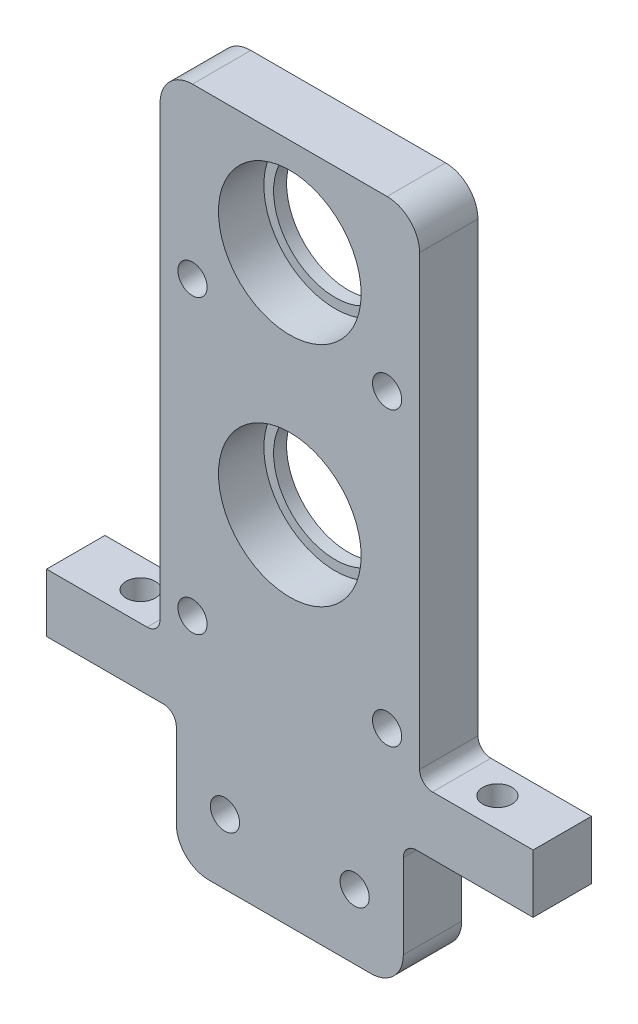
SolidWorks part; units mm, degrees
ref_plane "Plan de face" through (0, 0, 0) normal (0, 0, 1) x (1, 0, 0)
ref_plane "Plan de dessus" through (0, 0, 0) normal (0, 1, 0) x (1, 0, 0)
ref_plane "Plan de droite" through (0, 0, 0) normal (1, 0, 0) x (0, 0, -1)
sketch "Esquisse1" plane through (0, 0, 0) normal (0, 0, 1) x (1, 0, 0)
  line L1 (0, 0) -> (75, 0)
  line L2 (0, 0) -> (0, 85)
  line L3 (0, 85) -> (75, 85)
  line L4 (75, 0) -> (75, 85)
  dimension "D1" = 75
  dimension "D2" = 85
extrude "Boss.-Extru.1" add sketch "Esquisse1" along normal blind 9
sketch "Esquisse2" plane through (0, 0, 9) normal (0, 0, 1) x (1, 0, 0)
  line L0 (0, 0) -> (75, 0) construction
  line L1 (20, 0) -> (55, 0)
  line L2 (20, 0) -> (20, -20)
  line L3 (20, -20) -> (55, -20)
  line L4 (55, 0) -> (55, -20)
  line L5 (37.5, 0) -> (37.5, -20) construction
  dimension "D1" = 20
  dimension "D2" = 35
extrude "Boss.-Extru.2" add sketch "Esquisse2" against normal up to vertex (9 mm away) up to point (75, 0, 0)
sketch "Esquisse3" plane through (0, 0, 9) normal (0, 0, 1) x (1, 0, 0)
  line L0 (37.5, 70) -> (37.5, 0) construction
  line L1 (20, 0) -> (37.5, 0) construction
  line L2 (37.5, 0) -> (55, 0) construction
  line L3 (37.5, 70) -> (37.5, 85) construction
  line L4 (75, 85) -> (0, 85) construction
  circle A0 centre (37.5, 70) radius 11
  circle A1 centre (37.5, 35) radius 11
  dimension "D2" = 22
  dimension "D3" = 35
  dimension "D1" = 70
extrude "Enlèv. mat.-Extru.1" cut sketch "Esquisse3" against normal blind 7
sketch "Esquisse4" plane through (0, 0, 9) normal (0, 0, 1) x (1, 0, 0)
  circle A0 centre (37.5, 70) radius 9.5
  circle A1 centre (37.5, 70) radius 11 construction
  circle A2 centre (37.5, 35) radius 9.5
  circle A3 centre (37.5, 35) radius 11 construction
  dimension "D1" = 1.5
  dimension "D2" = 1.5
extrude "Enlèv. mat.-Extru.2" cut sketch "Esquisse4" against normal through all
sketch "Esquisse5" plane through (0, 0, 9) normal (0, 0, 1) x (1, 0, 0)
  line L0 (37.5, -20) -> (37.5, 85) construction
  line L1 (20, -20) -> (55, -20) construction
  line L2 (75, 85) -> (0, 85) construction
  line L4 (75, 9) -> (57.5, 9)
  line L5 (75, 9) -> (75, 85)
  line L6 (75, 85) -> (57.5, 85)
  line L7 (57.5, 9) -> (57.5, 85)
  line L8 (55, 0) -> (75, 0) construction
  line L9 (17.5, 9) -> (17.5, 85)
  line L10 (0, 85) -> (17.5, 85)
  line L11 (0, 9) -> (0, 85)
  line L12 (0, 9) -> (17.5, 9)
  line L13 (75, 0) -> (75, 85) construction
  point P12 (57.5, 47)
  dimension "D1" = 40
  dimension "D2" = 9
extrude "Enlèv. mat.-Extru.3" cut sketch "Esquisse5" against normal through all both and the other way through all
fillet "Congé1" radius 2 4 edges at (57.5, 9, 4.5) (55, 0, 4.5) (20, 0, 4.5) (17.5, 9, 4.5)
fillet "Congé2" radius 5 4 edges at (55, -20, 4.5) (20, -20, 4.5) (17.5, 85, 4.5) (57.5, 85, 4.5)
sketch "Esquisse6" plane through (0, 0, 9) normal (0, 0, 1) x (1, 0, 0)
  line L0 (20, -10) -> (55, -10) construction
  line L1 (20, -2) -> (20, -15) construction
  line L2 (55, -15) -> (55, -2) construction
  line L3 (57, 0) -> (75, 0) construction
  line L4 (37.5, -10) -> (37.5, -20) construction
  line L5 (25, -20) -> (50, -20) construction
  line L6 (17.5, 14) -> (22.5, 14) construction
  line L7 (17.5, 80) -> (17.5, 11) construction
  line L8 (22.5, 14) -> (22.5, 59) construction
  line L9 (22.5, 59) -> (17.5, 59) construction
  line L10 (15.5, 9) -> (0, 9) construction
  line L11 (52.5, 59) -> (57.5, 59) construction
  line L12 (52.5, 14) -> (52.5, 59) construction
  line L13 (57.5, 14) -> (52.5, 14) construction
  circle A0 centre (47.5, -10) radius 2.25
  circle A1 centre (27.5, -10) radius 2.25
  circle A2 centre (22.5, 59) radius 2.25
  circle A3 centre (22.5, 14) radius 2.25
  circle A4 centre (52.5, 14) radius 2.25
  circle A5 centre (52.5, 59) radius 2.25
  dimension "D2" = 4.5
  dimension "D3" = 10
  dimension "D7" = 4.5
  dimension "D1" = 10
  dimension "D4" = 5
  dimension "D5" = 45
  dimension "D6" = 5
extrude "Enlèv. mat.-Extru.4" cut sketch "Esquisse6" against normal through all
sketch "Esquisse7" plane through (0, 9, 0) normal (0, 1, 0) x (1, 0, 0)
  line L0 (10, 0) -> (10, -9) construction
  line L1 (0, 0) -> (15.5, 0) construction
  line L2 (15.5, -9) -> (0, -9) construction
  line L3 (20, -9) -> (20, 0) construction
  line L5 (37.5, -9) -> (37.5, 0) construction
  line L6 (52.5, -9) -> (22.5, -9) construction
  line L7 (52.5, 0) -> (22.5, 0) construction
  line L8 (65, 0) -> (65, -9) construction
  circle A0 centre (10, -4.5) radius 2.25
  circle A1 centre (65, -4.5) radius 2.25
  dimension "D1" = 4.5
  dimension "D2" = 10
extrude "Enlèv. mat.-Extru.5" cut sketch "Esquisse7" against normal through all
